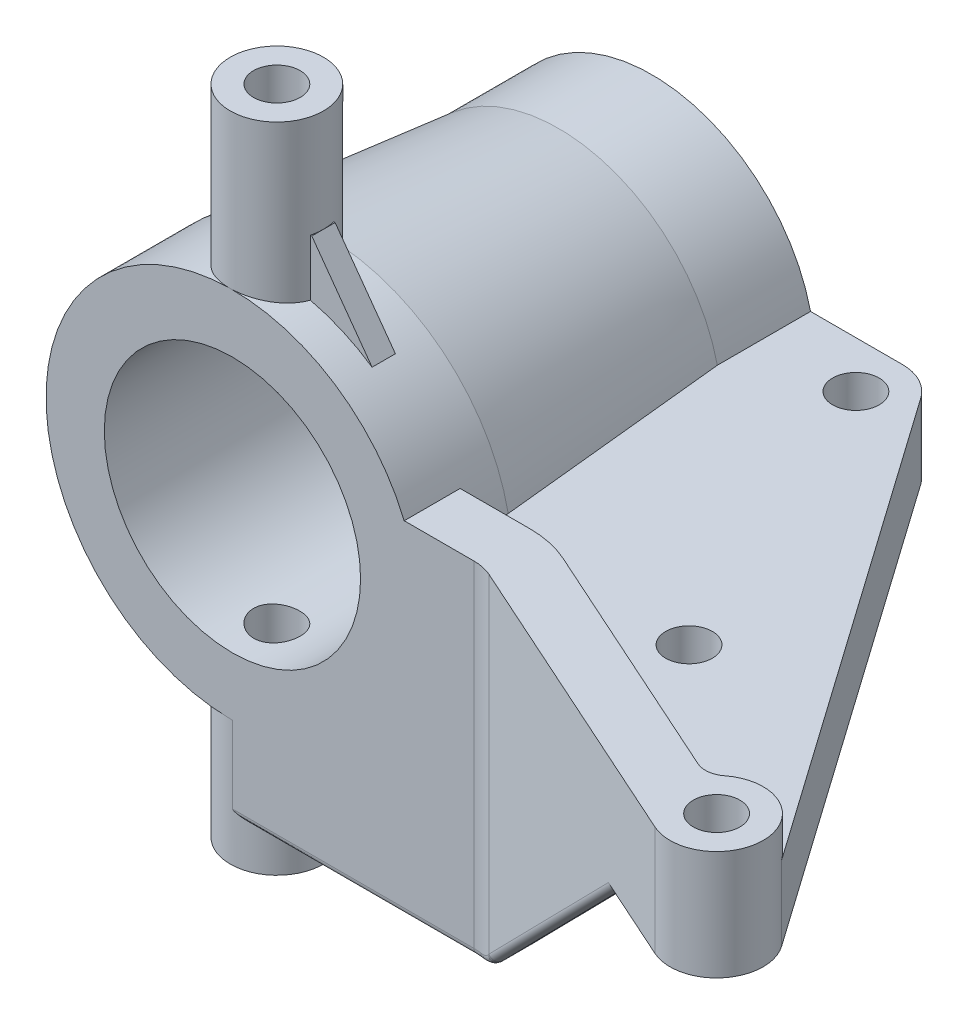
SolidWorks part; units mm, degrees
ref_plane "Front Plane" through (0, 0, 0) normal (0, 0, 1) x (1, 0, 0)
ref_plane "Top Plane" through (0, 0, 0) normal (0, 1, 0) x (1, 0, 0)
ref_plane "Right Plane" through (0, 0, 0) normal (1, 0, 0) x (0, 0, -1)
sketch "Sketch1" plane through (0, 0, 0) normal (0, 1, 0) x (1, 0, 0)
  line L0 (0, 0) -> (0, 22.86)
  line L1 (0, 22.86) -> (5.0315, 22.86)
  line L2 (7.1088, 21.7818) -> (25.1437, -3.8468)
  line L3 (22.0241, -7.6249) -> (5.5772, -0.2237)
  line L4 (0, 0) -> (4.5348, 0)
  arc A0 (25.1437, -3.8468) -> (22.0241, -7.6249) centre (23.0665, -5.3086) cw
  arc A1 (5.0315, 22.86) -> (7.1088, 21.7818) centre (5.0315, 20.32) cw
  arc A2 (5.5772, -0.2237) -> (4.5348, 0) centre (4.5348, -2.54) ccw
  circle A3 centre (23.0665, -5.3086) radius 1.27
  circle A4 centre (5.0315, 20.32) radius 1.27
  circle A5 centre (12.4437, 3.81) radius 1.27
  point P13 (30.48, -11.43)
  point P16 (6.35, 22.86)
  point P19 (5.08, 0)
  dimension "D6" = 2.54
  dimension "D7" = 2.54
  dimension "D8" = 2.54
  dimension "D9" = 2.54
  dimension "D10" = 2.54
  dimension "D11" = 2.54
  dimension "D1" = 6.35
  dimension "D2" = 22.86
  dimension "D3" = 5.08
  dimension "D4" = 34.29
  dimension "D5" = 30.48
  dimension "D12" = 19.05
  dimension "D13" = 12.7
extrude "Boss-Extrude1" add sketch "Sketch1" along normal mid plane 4.064
sketch "Sketch2" plane through (0, 2.032, 0) normal (0, 1, 0) x (1, 0, 0)
  line L0 (18.0967, -5.8575) -> (5.5772, -0.2237)
  line L1 (5.5772, -0.2237) -> (22.0241, -7.6249) construction
  line L2 (4.5348, 0) -> (-8.636, 0)
  line L3 (18.0967, -3.3507) -> (18.0967, -5.8575)
  line L4 (18.0967, -3.3507) -> (6.5152, 1.8609)
  line L5 (6.5152, 1.8609) -> (5.5772, -0.2237) construction
  line L6 (4.5348, 2.286) -> (-8.636, 2.286)
  line L7 (-8.636, 2.286) -> (-8.636, 0)
  line L8 (0, 22.86) -> (0, 0) construction
  arc A0 (5.5772, -0.2237) -> (4.5348, 0) centre (4.5348, -2.54) ccw
  arc A1 (4.5348, 2.286) -> (6.5152, 1.8609) centre (4.5348, -2.54) cw
  line M6 (0, 0) -> (4.5348, 0)
  arc M7 (4.5348, 0) -> (5.5772, -0.2237) centre (4.5348, -2.54) cw
  line M8 (5.5772, -0.2237) -> (22.0241, -7.6249)
  line M13 (0, 22.86) -> (0, 0)
  dimension "D1" = 2.286
  dimension "D2" = 12.7
  dimension "D3" = 2.286
  dimension "D4" = 8.636
extrude "Boss-Extrude2" add sketch "Sketch2" along normal blind 12.7 contours L4 L5 L3 M8 | L5 A1 L6 M13 M6 M7 | L6 L7 L2 M13 region at (12.0684, 2.032, 1.9076) region at (3.0494, 2.032, -1.1445) region at (-4.318, 2.032, -1.143)
sketch "Sketch3" plane through (0, 0, -2.286) normal (0, 0, -1) x (-1, 0, 0)
  line L0 (-18.0967, 2.032) -> (-5.525, 14.732)
  line L1 (-4.5348, 14.732) -> (-6.5152, 14.732) construction
  line L2 (-18.0967, 2.032) -> (-18.0967, 14.732)
  line L3 (-18.0967, 14.732) -> (-5.525, 14.732)
extrude "Cut-Extrude1" cut sketch "Sketch3" against normal through all
sketch "Sketch4" plane through (0, 0, 0) normal (0, 1, 0) x (1, 0, 0)
  line L0 (-8.636, 22.86) -> (-8.636, 0) construction
  line L1 (-8.636, 0) -> (4.5348, 0) construction
  line L2 (0.254, 22.86) -> (0.254, 17.78)
  line L4 (0.254, 17.78) -> (1.524, 5.08)
  line L5 (1.524, 5.08) -> (1.524, 0)
  line L6 (0.254, 22.86) -> (-4.826, 22.86)
  line L7 (-4.826, 22.86) -> (-4.826, 0)
  line L8 (-4.826, 0) -> (1.524, 0)
  point P7 (-2.0506, 0)
  dimension "D1" = 8.636
  dimension "D2" = 10.16
  dimension "D3" = 5.08
  dimension "D4" = 5.08
  dimension "D5" = 7.62
  dimension "D6" = 0.254
revolve "Revolve1" add sketch "Sketch4" angle 360 about L0
sketch "Sketch8" plane through (0, 0, 0) normal (0, 1, 0) x (1, 0, 0)
  line L0 (-8.636, 0) -> (4.5348, 0) construction
  line L1 (-8.7537, 2.54) -> (-8.7537, 22.86) construction
  line L2 (0.0187, 22.86) -> (-17.526, 22.86) construction
  circle A0 centre (-8.7537, 2.54) radius 2.54
  dimension "D1" = 5.08
extrude "Boss-Extrude4" add sketch "Sketch8" along normal blind 17.018 and the other way blind 18.542
sketch "Sketch5" plane through (0, 0, -22.86) normal (0, 0, -1) x (-1, 0, 0)
  circle A0 centre (8.636, 0) radius 6.985
  dimension "D1" = 13.97
extrude "Cut-Extrude2" cut sketch "Sketch5" against normal through all
sketch "Sketch6" plane through (0, -2.032, 0) normal (0, -1, 0) x (1, 0, 0)
  line L0 (5.5772, 0.2237) -> (22.0241, 7.6249) construction
  line L1 (1.3187, 0) -> (4.5348, 0) construction
  line L3 (5.5772, 0.2237) -> (22.0241, 7.6249)
  line L4 (1.3187, 0) -> (4.5348, 0)
  line L5 (1.3187, -3.048) -> (0.508, -3.048)
  line L6 (20.202, 3.4625) -> (6.8279, -2.5558)
  line L7 (1.3187, -3.048) -> (4.5348, -3.048)
  line L8 (0.508, -3.048) -> (0.508, 0)
  line L9 (0.508, 0) -> (1.3187, 0)
  circle A0 centre (23.0665, 5.3086) radius 1.27
  arc A1 (21.5043, 3.3058) -> (22.0241, 7.6249) centre (23.0665, 5.3086) ccw
  circle A2 centre (23.0665, 5.3086) radius 1.27 construction
  arc A3 (25.1437, 3.8468) -> (22.0241, 7.6249) centre (23.0665, 5.3086) ccw construction
  arc A4 (4.5348, 0) -> (5.5772, 0.2237) centre (4.5348, 2.54) ccw construction
  arc A5 (4.5348, 0) -> (5.5772, 0.2237) centre (4.5348, 2.54) ccw
  arc A6 (4.5348, -3.048) -> (6.8279, -2.5558) centre (4.5348, 2.54) ccw
  arc A7 (20.202, 3.4625) -> (21.5043, 3.3058) centre (20.7232, 2.3044) cw
  dimension "D1" = 1.27
  dimension "D3" = 0.508
  dimension "D2" = 3.048
extrude "Boss-Extrude3" add sketch "Sketch6" along normal blind 1.905
ref_plane "Plane2" through (0, 0, -2.54) normal (0, 0, 1) x (1, 0, 0)
sketch "Sketch10" plane through (0, 0, -2.54) normal (0, 0, 1) x (1, 0, 0)
  line L0 (-6.2137, -12.954) -> (-2.9278, -8.4049)
  line L1 (-2.9278, -8.4049) -> (-6.8487, -8.4049)
  line L2 (-6.2137, -12.954) -> (-6.8487, -12.954)
  line L4 (-6.8487, -12.954) -> (-6.8487, -8.4049)
  line L5 (-6.2137, -18.542) -> (-6.2137, -9.867) construction
  arc A0 (-8.7537, -10.1593) -> (0.7302, -3.937) centre (-8.636, 0) ccw construction
  dimension "D1" = 4.5491
  dimension "D2" = 0.635
  dimension "D3" = 5.588
extrude "Boss-Extrude7" add sketch "Sketch10" along normal mid plane 1.27
fillet "Fillet1" radius 1.27 1 edges at (5.525, 14.732, -0.9912)
fillet "Fillet2" radius 0.381 10 edges at (-2.0506, 14.732, 0) (4.766, 14.732, 0.0105) (5.1926, 14.7166, 0.0866) (5.7467, 14.4858, 0.3) (-0.8458, 14.732, -2.286) (4.7653, 14.732, -2.2805) (5.4133, 14.6612, -2.2054) (6.2104, 14.0396, -1.9858) (11.9972, 8.1937, 3.1127) (12.3059, 7.8818, 0.7449)
sketch "Sketch11" plane through (0, 17.018, 0) normal (0, 1, 0) x (1, 0, 0)
  circle A0 centre (-8.7537, 2.54) radius 1.27
  circle A1 centre (-8.7537, 2.54) radius 2.54 construction
  dimension "D1" = 2.54
extrude "Cut-Extrude4" cut sketch "Sketch11" against normal through all
mirror "Mirror1" about plane through (-8.7537, 17.018, -2.54) normal (0, 1, 0) of bodies 110
sketch "Sketch12" plane through (0, 0, -22.86) normal (0, 0, -1) x (-1, 0, 0)
  line L0 (-16.1262, 32.004) -> (-16.1262, 2.032) construction
  line L1 (25.4, 17.018) -> (-31.75, 17.018)
  line L2 (25.4, 17.018) -> (25.4, -25.4)
  line L3 (25.4, -25.4) -> (-31.75, -25.4)
  line L4 (-31.75, 17.018) -> (-31.75, -25.4)
  line L5 (-25.1437, 32.004) -> (-7.1088, 32.004) construction
  line L6 (-25.1437, 2.032) -> (-7.1088, 2.032) construction
  point P11 (-16.1262, 17.018)
  dimension "D1" = 25.4
  dimension "D2" = 31.75
  dimension "D3" = 25.4
extrude "Cut-Extrude5" cut sketch "Sketch12" against normal through all
